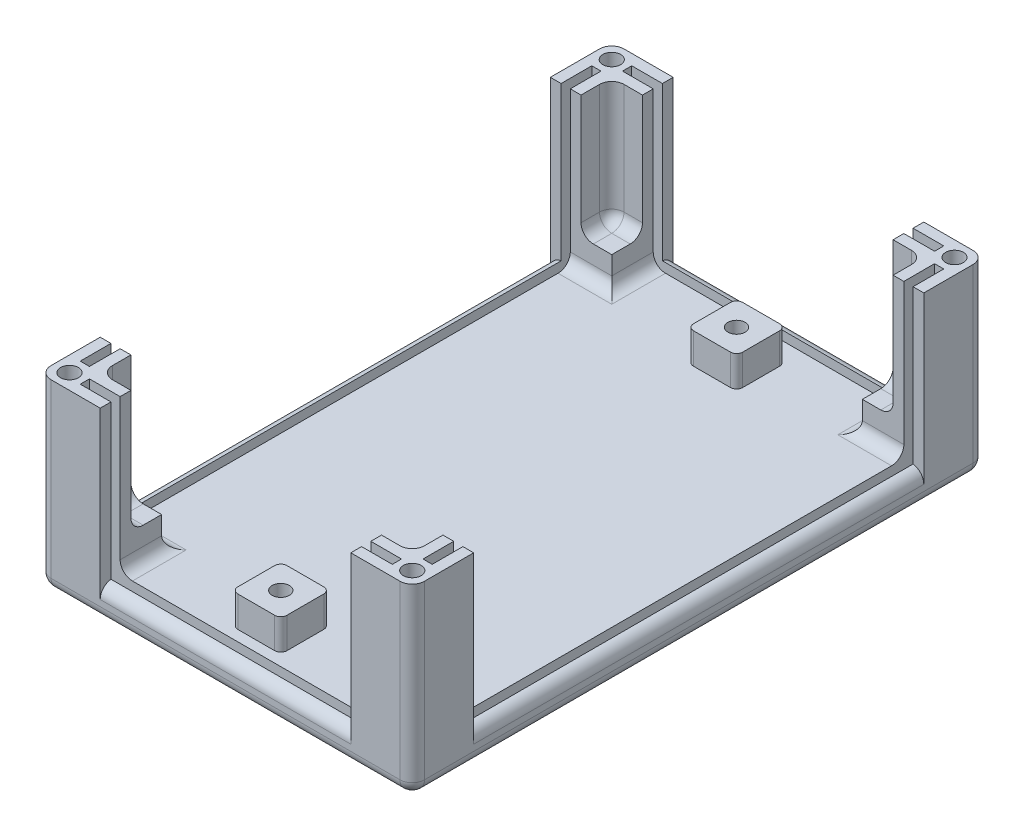
SolidWorks part; units mm, degrees
ref_plane "Front Plane" through (0, 0, 0) normal (0, 0, 1) x (1, 0, 0)
ref_plane "Top Plane" through (0, 0, 0) normal (0, 1, 0) x (1, 0, 0)
ref_plane "Right Plane" through (0, 0, 0) normal (1, 0, 0) x (0, 0, -1)
sketch "Sketch1" plane through (0, 0, 0) normal (0, 1, 0) x (1, 0, 0)
  line L0 (30.4, -46.64) -> (30.4, 46.64)
  line L1 (-25.4, -41.64) -> (25.4, -41.64)
  line L2 (-25.4, -41.64) -> (-25.4, 41.64)
  line L3 (-25.4, 41.64) -> (25.4, 41.64)
  line L4 (25.4, -41.64) -> (25.4, 41.64)
  line L5 (-25.4, -41.64) -> (25.4, 41.64) construction
  line L6 (-25.4, 41.64) -> (25.4, -41.64) construction
  line L13 (-30.4, 46.64) -> (30.4, 46.64)
  line L14 (-30.4, -46.64) -> (-30.4, 46.64)
  line L15 (-30.4, -46.64) -> (30.4, -46.64)
  line L16 (-20.4, 41.64) -> (-20.4, 46.64)
  line L17 (-25.4, 36.64) -> (-30.4, 36.64)
  line L18 (0, -46.64) -> (0, 46.64) construction
  line L19 (-30.4, 0) -> (30.4, 0) construction
  line L20 (25.4, 36.64) -> (30.4, 36.64)
  line L21 (20.4, 41.64) -> (20.4, 46.64)
  line L22 (-20.4, -41.64) -> (-20.4, -46.64)
  line L23 (-25.4, -36.64) -> (-30.4, -36.64)
  line L24 (25.4, -36.64) -> (30.4, -36.64)
  line L25 (20.4, -41.64) -> (20.4, -46.64)
  line L27 (-4, -41.64) -> (4, -41.64)
  line L28 (-4, -41.64) -> (-4, -33.64)
  line L29 (-4, -33.64) -> (4, -33.64)
  line L30 (4, -41.64) -> (4, -33.64)
  line L31 (-4, -41.64) -> (4, -33.64) construction
  line L32 (-4, -33.64) -> (4, -41.64) construction
  line L33 (3.1754, -37.64) -> (1.5877, -34.89)
  line L34 (1.5877, -34.89) -> (-1.5877, -34.89)
  line L35 (-1.5877, -34.89) -> (-3.1754, -37.64)
  line L36 (-3.1754, -37.64) -> (-1.5877, -40.39)
  line L37 (-1.5877, -40.39) -> (1.5877, -40.39)
  line L38 (1.5877, -40.39) -> (3.1754, -37.64)
  line L39 (-4, 32.56) -> (4, 32.56)
  line L40 (-4, 32.56) -> (-4, 40.56)
  line L41 (-4, 40.56) -> (4, 40.56)
  line L42 (4, 32.56) -> (4, 40.56)
  line L43 (-4, 32.56) -> (4, 40.56) construction
  line L44 (-4, 40.56) -> (4, 32.56) construction
  line L45 (3.1754, 36.56) -> (1.5877, 39.31)
  line L46 (1.5877, 39.31) -> (-1.5877, 39.31)
  line L47 (-1.5877, 39.31) -> (-3.1754, 36.56)
  line L48 (-3.1754, 36.56) -> (-1.5877, 33.81)
  line L49 (-1.5877, 33.81) -> (1.5877, 33.81)
  line L50 (1.5877, 33.81) -> (3.1754, 36.56)
  circle A0 centre (0, -37.64) radius 1.4
  circle A1 centre (0, 36.56) radius 1.4
  circle A2 centre (0, -37.64) radius 2.75 construction
  circle A3 centre (0, 36.56) radius 2.75 construction
  point P0 (0, 0)
  dimension "D3" = 2.8
  dimension "D5" = 2.8
  dimension "D1" = 50.8
  dimension "D6" = 74.2
  dimension "D2" = 83.28
  dimension "D4" = 9
  dimension "D7" = 10
  dimension "D9" = 10
  dimension "D10" = 8
  dimension "D11" = 8
  dimension "D12" = 5.5
  dimension "D13" = 8
  dimension "D14" = 8
  dimension "D15" = 5.5
  dimension "D8" = 5
extrude "Boss-Extrude1" add sketch "Sketch1" along normal blind 5 contours L23 L2 L17 L14 | L2 L23 L14 L15 L22 L1 | L30 L27 L28 L1 L22 L15 L25 | L1 L25 L15 L0 L24 L4 | L4 L24 L0 L20 | L30 L1 L4 L3 L2 L28 L29 L42 L39 L40 L41 | L21 L3 L4 L20 L0 L13 | L3 L21 L13 L16 | L17 L2 L3 L16 L13 L14 | L39 L42 L41 L40 L50 L49 L48 L47 L46 L45 | L49 L50 L45 L46 L47 L48 A1 | L38 L1 L30 L29 L28 L36 L35 L34 L33 | L1 L38 L33 L34 L35 L36 A0 | L38 L37 L36 L1 L28 L27 L30 | L37 L38 L1 L36 | L3 L42 L41 L40 region at (26.2333, 0, 42.4733) region at (27.9, 0, 0) region at (0, 0, 44.14) region at (26.2333, 0, -42.4733) region at (0, 0, -0.0168) region at (-26.2333, 0, 42.4733) region at (0, 0, 41.5269) region at (0, 0, -44.14) region at (-27.9, 0, 0) region at (-26.2333, 0, -42.4733) region at (2.3088, 0, 38.973) region at (-3.8869, 0, -36.56) region at (2.3088, 0, -35.227)
extrude "Boss-Extrude3" add sketch "Sketch1<4>" along normal blind 30 contours L17 L2 L3 L16 L13 L14 | L21 L3 L4 L20 L0 L13 | L1 L25 L15 L0 L24 L4 | L2 L23 L14 L15 L22 L1 region at (26.2333, 0, 42.4733) region at (26.2333, 0, -42.4733) region at (-26.2333, 0, 42.4733) region at (-26.2333, 0, -42.4733)
sketch "Sketch1<4>" plane through (0, 0, 0) normal (0, 1, 0) x (1, 0, 0) same geometry as "Sketch1"
extrude "Boss-Extrude4" add sketch "Sketch1<6>" along normal blind 5 from surface contours L38 L1 L30 L29 L28 L36 L35 L34 L33 | L39 L42 L3 L40 L50 L49 L48 L47 L46 L45 | L37 L38 L33 L34 L35 L36 A0 | L49 L50 L45 L46 L47 L48 A1 region at (0, 0, 41.5269) region at (2.3088, 0, 38.973) region at (-3.8869, 0, -36.56) region at (2.3088, 0, -35.227) starting at face at (0, 5, 39.04)
sketch "Sketch1<6>" plane through (0, 0, 0) normal (0, 1, 0) x (1, 0, 0) same geometry as "Sketch1"
extrude "Cut-Extrude4" cut sketch "Sketch1<8>" along normal blind 2.3 contours L37 L38 L33 L34 L35 L36 A0 | L49 L50 L45 L46 L47 L48 A1 region at (2.3088, 0, 38.973) region at (2.3088, 0, -35.227)
sketch "Sketch1<8>" plane through (0, 0, 0) normal (0, 1, 0) x (1, 0, 0) same geometry as "Sketch1"
sketch "Sketch4" plane through (0, 5, 0) normal (0, 1, 0) x (1, 0, 0)
  line L0 (-30.4, 0) -> (30.4, 0) construction
  line L1 (-25.4, -41.64) -> (-20.4, -41.64)
  line L2 (-25.4, -41.64) -> (-25.4, -36.64)
  line L3 (-25.4, -36.64) -> (-20.4, -36.64)
  line L4 (-20.4, -41.64) -> (-20.4, -36.64)
  line L5 (-30.4, -36.64) -> (-30.4, 36.64) construction
  line L6 (30.4, -36.64) -> (30.4, 36.64) construction
  line L7 (0, -46.64) -> (0, 46.64) construction
  line L8 (-20.4, -46.64) -> (20.4, -46.64) construction
  line L9 (-20.4, 46.64) -> (20.4, 46.64) construction
  line L10 (-25.4, 41.64) -> (-20.4, 41.64)
  line L11 (-25.4, 41.64) -> (-25.4, 36.64)
  line L12 (-25.4, 36.64) -> (-20.4, 36.64)
  line L13 (-20.4, 41.64) -> (-20.4, 36.64)
  line L14 (25.4, 41.64) -> (25.4, 36.64)
  line L15 (25.4, 41.64) -> (20.4, 41.64)
  line L16 (20.4, 41.64) -> (20.4, 36.64)
  line L17 (25.4, 36.64) -> (20.4, 36.64)
  line L18 (25.4, -41.64) -> (25.4, -36.64)
  line L19 (25.4, -41.64) -> (20.4, -41.64)
  line L20 (20.4, -41.64) -> (20.4, -36.64)
  line L21 (25.4, -36.64) -> (20.4, -36.64)
  dimension "D1" = 5
  dimension "D2" = 5
extrude "Boss-Extrude5" add sketch "Sketch4" along normal blind 5
sketch "Sketch2" plane through (0, 30, 0) normal (0, 1, 0) x (1, 0, 0)
  line L0 (-30.4, 46.64) -> (-20.4, 46.64) construction
  line L1 (-30.4, 46.64) -> (-20.4, 46.64)
  line L2 (20.4, 46.64) -> (30.4, 46.64) construction
  line L3 (30.4, 36.64) -> (30.4, 46.64) construction
  line L4 (-30.4, -46.64) -> (-20.4, -46.64) construction
  line L5 (30.4, -46.64) -> (30.4, -36.64) construction
  line L6 (20.4, -46.64) -> (30.4, -46.64) construction
  line L7 (30.4, -36.64) -> (30.4, 36.64) construction
  line L8 (-20.4, -46.64) -> (20.4, -46.64) construction
  line L9 (-30.4, -46.64) -> (-30.4, -36.64) construction
  line L10 (-30.4, -36.64) -> (-30.4, 36.64) construction
  line L11 (-30.4, 36.64) -> (-30.4, 46.64) construction
  line L12 (-20.4, 46.64) -> (20.4, 46.64) construction
  line L13 (20.4, 46.64) -> (30.4, 46.64)
  line L14 (30.4, 36.64) -> (30.4, 46.64)
  line L15 (-30.4, -46.64) -> (-20.4, -46.64)
  line L16 (30.4, -46.64) -> (30.4, -36.64)
  line L17 (20.4, -46.64) -> (30.4, -46.64)
  line L18 (30.4, -36.64) -> (30.4, 36.64)
  line L19 (-20.4, -46.64) -> (20.4, -46.64)
  line L20 (-30.4, -46.64) -> (-30.4, -36.64)
  line L21 (-30.4, -36.64) -> (-30.4, 36.64)
  line L22 (-30.4, 36.64) -> (-30.4, 46.64)
  line L23 (-20.4, 46.64) -> (20.4, 46.64)
  line L25 (-30.4, 44.89) -> (30.4, 44.89)
  line L26 (-30.4, 44.89) -> (-30.4, 43.39)
  line L27 (-30.4, 43.39) -> (30.4, 43.39)
  line L28 (30.4, 44.89) -> (30.4, 43.39)
  line L29 (-25.4, 41.64) -> (-25.4, 46.64)
  line L30 (-28.65, 46.64) -> (-27.15, 46.64)
  line L31 (-28.65, 46.64) -> (-28.65, -46.64)
  line L32 (-28.65, -46.64) -> (-27.15, -46.64)
  line L33 (-27.15, 46.64) -> (-27.15, -46.64)
  line L34 (-25.4, 41.64) -> (-30.4, 41.64)
  line L35 (0, 46.64) -> (0, -46.64) construction
  line L36 (-30.4, 0) -> (30.4, 0) construction
  line L37 (25.4, 41.64) -> (25.4, 46.64)
  line L38 (-25.4, -41.64) -> (-30.4, -41.64)
  line L39 (25.4, -41.64) -> (25.4, -46.64)
  line L40 (-25.4, -41.64) -> (-25.4, -46.64)
  line L41 (-30.4, -44.89) -> (30.4, -44.89)
  line L42 (-30.4, -43.39) -> (30.4, -43.39)
  line L43 (-25.4, 41.64) -> (-30.4, 41.64)
  line L44 (25.4, -41.64) -> (30.4, -41.64)
  line L45 (25.4, 41.64) -> (30.4, 41.64)
  line L46 (28.65, 46.64) -> (28.65, -46.64)
  line L47 (27.15, 46.64) -> (27.15, -46.64)
  line L48 (25.4, -44.14) -> (30.4, -44.14) construction
  circle A0 centre (27.9, -44.14) radius 1.45
  circle A1 centre (-27.9, -44.14) radius 1.45
  circle A2 centre (-27.9, 44.14) radius 1.45
  circle A3 centre (27.9, 44.14) radius 1.45
  point P52 (27.9, -44.14)
  line M14 (-30.4, 36.64) -> (-25.4, 36.64)
  line M17 (-20.4, 41.64) -> (-20.4, 46.64)
  dimension "D5" = 2.9
  dimension "D1" = 1.5
  dimension "D2" = 1.75
  dimension "D3" = 1.5
  dimension "D4" = 1.75
extrude "Cut-Extrude1" cut sketch "Sketch2" against normal offset from surface (27 mm away) 2 contours L45 L47 L44 L46 | L42 L40 L41 L39 | L38 L33 L31 M14 | L27 L37 L25 M17 | L29 L27 L25 M17 | L33 L34 L31 M14 region at (-22.9, 30, -44.14) region at (-27.9, 30, -39.14) region at (2.5, 30, -44.14) region at (-27.9, 30, 2.5) region at (27.9, 30, 0) region at (0, 30, 44.14) up to face at (0, 5, 37.64) offset beyond the face yes
extrude "Cut-Extrude2" cut sketch "Sketch2<3>" against normal blind 15 contours A0 | A1 | A2 | A3
sketch "Sketch2<3>" plane through (0, 30, 0) normal (0, 1, 0) x (1, 0, 0) same geometry as "Sketch2"
sketch "Sketch3" plane through (0, 0, 0) normal (0, -1, 0) x (1, 0, 0)
  line L1 (-17, -17) -> (17, -17)
  line L2 (-17, -17) -> (-17, 17)
  line L3 (-17, 17) -> (17, 17)
  line L4 (17, -17) -> (17, 17)
  line L5 (-17, -17) -> (17, 17) construction
  line L6 (-17, 17) -> (17, -17) construction
  point P0 (0, 0)
  dimension "D1" = 34
  dimension "D2" = 34
extrude "Cut-Extrude3" cut sketch "Sketch3" against normal blind 2
fillet "Fillet1" radius 2 16 edges at (-25.4, 20, 41.64) (-25.4, 20, -41.64) (25.4, 20, 41.64) (25.4, 20, -41.64) (0, 5, -46.64) (30.4, 5, 0) (0, 5, 46.64) (-30.4, 5, 0) (30.4, 15, 46.64) (-30.4, 15, 46.64) (-30.4, 15, -46.64) (30.4, 15, -46.64) (0, 0, -46.64) (-30.4, 0, 0) (0, 0, 46.64) (30.4, 0, 0)
fillet "Fillet3" radius 1 8 edges at (-4, 7.5, 33.64) (4, 7.5, 33.64) (-4, 7.5, -32.56) (-4, 7.5, -40.56) (4, 7.5, -32.56) (4, 7.5, -40.56) (-4, 7.5, 41.64) (4, 7.5, 41.64)
fillet "Fillet5" radius 4 4 edges at (17, 1, -17) (-17, 1, -17) (-17, 1, 17) (17, 1, 17)
fillet "Fillet6" radius 2 20 edges at (-21.9, 10, -41.64) (-25.4, 10, -38.14) (25.4, 10, -38.14) (21.9, 10, -41.64) (-25.4, 10, 38.14) (-21.9, 10, 41.64) (21.9, 10, 41.64) (25.4, 10, 38.14) (-24.8142, 10, -41.0542) (-20.4, 5, -40.015) (-23.775, 5, -36.64) (24.8142, 10, -41.0542) (23.775, 5, -36.64) (20.4, 5, -40.015) (-24.8142, 10, 41.0542) (-23.775, 5, 36.64) (-20.4, 5, 40.015) (24.8142, 10, 41.0542) (20.4, 5, 40.015) (23.775, 5, 36.64)
equation "\"D2@Sketch1\"=81.28mm+2"
